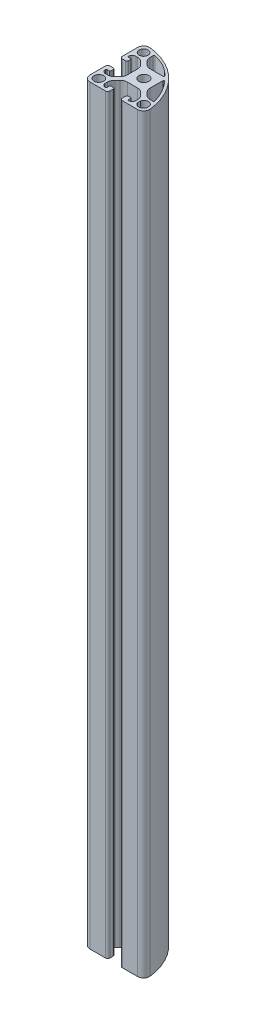
SolidWorks part; units mm, degrees
ref_plane "Alzado" through (0, 0, 0) normal (0, 0, 1) x (1, 0, 0)
ref_plane "Planta" through (0, 0, 0) normal (0, 1, 0) x (1, 0, 0)
ref_plane "Vista lateral" through (0, 0, 0) normal (1, 0, 0) x (0, 0, -1)
sketch "Croquis1" plane through (0, 0, 0) normal (0, 1, 0) x (1, 0, 0)
  line L0 (-18.2, 12.3) -> (-18.2, 15.7771)
  line L1 (-12.3, 11.8) -> (-17.7, 11.8)
  line L2 (-11.8, 16.9053) -> (-11.8, 12.3)
  line L3 (11.8, -17.7) -> (11.8, -12.3)
  line L4 (15.7771, -18.2) -> (12.3, -18.2)
  line L5 (12.3, -11.8) -> (16.9053, -11.8)
  line L6 (-18.2, -16) -> (-18.2, -12.3)
  line L7 (-12.3, -18.2) -> (-16, -18.2)
  line L8 (-11.8, -12.3) -> (-11.8, -17.7)
  line L9 (-17.7, -11.8) -> (-12.3, -11.8)
  line L10 (-10.1, 14.2924) -> (-10.1, 16.2371)
  line L11 (-6.9431, 9.0645) -> (-8.6355, 10.7569)
  line L12 (5.1332, 7.6) -> (-3.4076, 7.6)
  line L13 (4.1, -16.35) -> (4.1, -18.5)
  line L14 (5.6, -20) -> (15.7771, -20)
  line L15 (-20, 15.7771) -> (-20, 5.6)
  line L16 (-18.5, 4.1) -> (-16.35, 4.1)
  line L17 (-15.35, 5.1) -> (-15.35, 6.6)
  line L18 (-15.85, 7.1) -> (-17.5, 7.1)
  line L19 (-15.5, 10.1) -> (-14.2924, 10.1)
  line L20 (-10.7569, 8.6355) -> (-9.0645, 6.9431)
  line L21 (-7.6, 3.4076) -> (-7.6, -3.4076)
  line L22 (-9.0645, -6.9431) -> (-10.7569, -8.6355)
  line L23 (-14.2924, -10.1) -> (-15.5, -10.1)
  line L24 (-17.5, -7.1) -> (-15.85, -7.1)
  line L25 (-15.35, -6.6) -> (-15.35, -5.1)
  line L26 (-16.35, -4.1) -> (-18.5, -4.1)
  line L27 (-20, -5.6) -> (-20, -16)
  line L28 (-16, -20) -> (-5.6, -20)
  line L29 (-4.1, -18.5) -> (-4.1, -16.35)
  line L30 (-5.1, -15.35) -> (-6.6, -15.35)
  line L31 (-7.1, -15.85) -> (-7.1, -17.5)
  line L32 (-10.1, -15.5) -> (-10.1, -14.2924)
  line L33 (-8.6355, -10.7569) -> (-6.9431, -9.0645)
  line L34 (-3.4076, -7.6) -> (3.4076, -7.6)
  line L35 (6.9431, -9.0645) -> (8.6355, -10.7569)
  line L36 (10.1, -14.2924) -> (10.1, -15.5)
  line L37 (7.1, -17.5) -> (7.1, -15.85)
  line L38 (6.6, -15.35) -> (5.1, -15.35)
  line L39 (16.2371, -10.1) -> (14.2924, -10.1)
  line L40 (10.7569, -8.6355) -> (9.0645, -6.9431)
  line L41 (7.6, -3.4076) -> (7.6, 5.1332)
  circle A0 centre (0, 0) radius 3.35
  arc A1 (-15.7556, 17.9635) -> (-18.2, 15.7771) centre (-16, 15.7771) ccw
  arc A2 (-18.2, 12.3) -> (-17.7, 11.8) centre (-17.7, 12.3) ccw
  arc A3 (-12.3, 11.8) -> (-11.8, 12.3) centre (-12.3, 12.3) ccw
  arc A4 (-11.8, 16.9053) -> (-12.1979, 17.3947) centre (-12.3, 16.9053) ccw
  arc A5 (-12.1979, 17.3947) -> (-15.7556, 17.9635) centre (-20, -20) ccw
  arc A6 (12.3, -11.8) -> (11.8, -12.3) centre (12.3, -12.3) ccw
  arc A7 (11.8, -17.7) -> (12.3, -18.2) centre (12.3, -17.7) ccw
  arc A8 (15.7771, -18.2) -> (17.9635, -15.7556) centre (15.7771, -16) ccw
  arc A9 (17.9635, -15.7556) -> (17.3947, -12.1979) centre (-20, -20) ccw
  arc A10 (17.3947, -12.1979) -> (16.9053, -11.8) centre (16.9053, -12.3) ccw
  arc A11 (-17.7, -11.8) -> (-18.2, -12.3) centre (-17.7, -12.3) ccw
  arc A12 (-18.2, -16) -> (-16, -18.2) centre (-16, -16) ccw
  arc A13 (-12.3, -18.2) -> (-11.8, -17.7) centre (-12.3, -17.7) ccw
  arc A14 (-11.8, -12.3) -> (-12.3, -11.8) centre (-12.3, -12.3) ccw
  arc A15 (4.1, -18.5) -> (5.6, -20) centre (5.6, -18.5) ccw
  arc A16 (15.7771, -20) -> (19.7523, -15.5556) centre (15.7771, -16) ccw
  arc A17 (19.7523, -15.5556) -> (-15.5556, 19.7523) centre (-20, -20) ccw
  arc A18 (-15.5556, 19.7523) -> (-20, 15.7771) centre (-16, 15.7771) ccw
  arc A19 (-20, 5.6) -> (-18.5, 4.1) centre (-18.5, 5.6) ccw
  arc A20 (-16.35, 4.1) -> (-15.35, 5.1) centre (-16.35, 5.1) ccw
  arc A21 (-15.35, 6.6) -> (-15.85, 7.1) centre (-15.85, 6.6) ccw
  arc A22 (-18, 7.6) -> (-17.5, 7.1) centre (-17.5, 7.6) ccw
  arc A23 (-15.5, 10.1) -> (-18, 7.6) centre (-15.5, 7.6) ccw
  arc A24 (-10.7569, 8.6355) -> (-14.2924, 10.1) centre (-14.2924, 5.1) ccw
  arc A25 (-7.6, 3.4076) -> (-9.0645, 6.9431) centre (-12.6, 3.4076) ccw
  arc A26 (-9.0645, -6.9431) -> (-7.6, -3.4076) centre (-12.6, -3.4076) ccw
  arc A27 (-14.2924, -10.1) -> (-10.7569, -8.6355) centre (-14.2924, -5.1) ccw
  arc A28 (-18, -7.6) -> (-15.5, -10.1) centre (-15.5, -7.6) ccw
  arc A29 (-17.5, -7.1) -> (-18, -7.6) centre (-17.5, -7.6) ccw
  arc A30 (-15.85, -7.1) -> (-15.35, -6.6) centre (-15.85, -6.6) ccw
  arc A31 (-15.35, -5.1) -> (-16.35, -4.1) centre (-16.35, -5.1) ccw
  arc A32 (-18.5, -4.1) -> (-20, -5.6) centre (-18.5, -5.6) ccw
  arc A33 (-20, -16) -> (-16, -20) centre (-16, -16) ccw
  arc A34 (-5.6, -20) -> (-4.1, -18.5) centre (-5.6, -18.5) ccw
  arc A35 (-4.1, -16.35) -> (-5.1, -15.35) centre (-5.1, -16.35) ccw
  arc A36 (-6.6, -15.35) -> (-7.1, -15.85) centre (-6.6, -15.85) ccw
  arc A37 (-7.6, -18) -> (-7.1, -17.5) centre (-7.6, -17.5) ccw
  arc A38 (-10.1, -15.5) -> (-7.6, -18) centre (-7.6, -15.5) ccw
  arc A39 (-8.6355, -10.7569) -> (-10.1, -14.2924) centre (-5.1, -14.2924) ccw
  arc A40 (-3.4076, -7.6) -> (-6.9431, -9.0645) centre (-3.4076, -12.6) ccw
  arc A41 (6.9431, -9.0645) -> (3.4076, -7.6) centre (3.4076, -12.6) ccw
  arc A42 (10.1, -14.2924) -> (8.6355, -10.7569) centre (5.1, -14.2924) ccw
  arc A43 (7.6, -18) -> (10.1, -15.5) centre (7.6, -15.5) ccw
  arc A44 (7.1, -17.5) -> (7.6, -18) centre (7.6, -17.5) ccw
  arc A45 (7.1, -15.85) -> (6.6, -15.35) centre (6.6, -15.85) ccw
  arc A46 (5.1, -15.35) -> (4.1, -16.35) centre (5.1, -16.35) ccw
  arc A47 (-9.4621, 16.7177) -> (-10.1, 16.2371) centre (-9.6, 16.2371) ccw
  arc A48 (-10.1, 14.2924) -> (-8.6355, 10.7569) centre (-5.1, 14.2924) ccw
  arc A49 (-6.9431, 9.0645) -> (-3.4076, 7.6) centre (-3.4076, 12.6) ccw
  arc A50 (5.1332, 7.6) -> (5.4666, 8.4727) centre (5.1332, 8.1) ccw
  arc A51 (16.7177, -9.4621) -> (8.4727, 5.4666) centre (-20, -20) ccw
  arc A52 (16.2371, -10.1) -> (16.7177, -9.4621) centre (16.2371, -9.6) ccw
  arc A53 (10.7569, -8.6355) -> (14.2924, -10.1) centre (14.2924, -5.1) ccw
  arc A54 (7.6, -3.4076) -> (9.0645, -6.9431) centre (12.6, -3.4076) ccw
  arc A55 (8.4727, 5.4666) -> (7.6, 5.1332) centre (8.1, 5.1332) ccw
  arc A56 (-9.4621, 16.7177) -> (5.4666, 8.4727) centre (-14.5044, -10.0495) cw
extrude "Saliente-Extruir1" add sketch "Croquis1" along normal blind 500
sketch "Croquis2" plane through (0, 500, 0) normal (0, 1, 0) x (1, 0, 0)
  line L0 (-18.2, 15.7771) -> (-18.2, 12.3) construction
  line L1 (-17.7, 11.8) -> (-12.3, 11.8) construction
  line L2 (-11.8, 12.3) -> (-11.8, 16.9053) construction
  line L3 (-18.2, 15.7771) -> (-18.2, 12.3)
  line L4 (-17.7, 11.8) -> (-12.3, 11.8)
  line L5 (-11.8, 12.3) -> (-11.8, 16.9053)
  line L6 (-16, -18.2) -> (-12.3, -18.2) construction
  line L7 (-18.2, -12.3) -> (-18.2, -16) construction
  line L8 (-12.3, -11.8) -> (-17.7, -11.8) construction
  line L9 (-11.8, -17.7) -> (-11.8, -12.3) construction
  line L10 (-16, -18.2) -> (-12.3, -18.2)
  line L11 (-18.2, -12.3) -> (-18.2, -16)
  line L12 (-12.3, -11.8) -> (-17.7, -11.8)
  line L13 (-11.8, -17.7) -> (-11.8, -12.3)
  line L14 (12.3, -18.2) -> (15.7771, -18.2) construction
  line L15 (11.8, -12.3) -> (11.8, -17.7) construction
  line L16 (16.9053, -11.8) -> (12.3, -11.8) construction
  line L17 (12.3, -18.2) -> (15.7771, -18.2)
  line L18 (11.8, -12.3) -> (11.8, -13.9666)
  line L19 (16.9053, -11.8) -> (12.3, -11.8)
  line L20 (11.8, -16.0334) -> (11.8, -17.7)
  arc A0 (-11.8, 16.9053) -> (-12.1979, 17.3947) centre (-12.3, 16.9053) ccw construction
  arc A1 (-12.1979, 17.3947) -> (-15.7556, 17.9635) centre (-20, -20) ccw construction
  arc A2 (-15.7556, 17.9635) -> (-18.2, 15.7771) centre (-16, 15.7771) ccw construction
  arc A3 (-18.2, 12.3) -> (-17.7, 11.8) centre (-17.7, 12.3) ccw construction
  arc A4 (-12.3, 11.8) -> (-11.8, 12.3) centre (-12.3, 12.3) ccw construction
  arc A5 (-11.8, 16.9053) -> (-12.1979, 17.3947) centre (-12.3, 16.9053) ccw
  arc A6 (-12.1979, 17.3947) -> (-15.7556, 17.9635) centre (-20, -20) ccw
  arc A7 (-15.7556, 17.9635) -> (-18.2, 15.7771) centre (-16, 15.7771) ccw
  arc A8 (-18.2, 12.3) -> (-17.7, 11.8) centre (-17.7, 12.3) ccw
  arc A9 (-12.3, 11.8) -> (-11.8, 12.3) centre (-12.3, 12.3) ccw
  arc A10 (-12.3, -18.2) -> (-11.8, -17.7) centre (-12.3, -17.7) ccw construction
  arc A11 (-18.2, -16) -> (-16, -18.2) centre (-16, -16) ccw construction
  arc A12 (-17.7, -11.8) -> (-18.2, -12.3) centre (-17.7, -12.3) ccw construction
  arc A13 (-11.8, -12.3) -> (-12.3, -11.8) centre (-12.3, -12.3) ccw construction
  arc A14 (-12.3, -18.2) -> (-11.8, -17.7) centre (-12.3, -17.7) ccw
  arc A15 (-18.2, -16) -> (-16, -18.2) centre (-16, -16) ccw
  arc A16 (-17.7, -11.8) -> (-18.2, -12.3) centre (-17.7, -12.3) ccw
  arc A17 (-11.8, -12.3) -> (-12.3, -11.8) centre (-12.3, -12.3) ccw
  arc A18 (17.3947, -12.1979) -> (16.9053, -11.8) centre (16.9053, -12.3) ccw construction
  arc A19 (17.9635, -15.7556) -> (17.3947, -12.1979) centre (-20, -20) ccw construction
  arc A20 (15.7771, -18.2) -> (17.9635, -15.7556) centre (15.7771, -16) ccw construction
  arc A21 (11.8, -17.7) -> (12.3, -18.2) centre (12.3, -17.7) ccw construction
  arc A22 (12.3, -11.8) -> (11.8, -12.3) centre (12.3, -12.3) ccw construction
  arc A23 (17.3947, -12.1979) -> (16.9053, -11.8) centre (16.9053, -12.3) ccw
  arc A24 (17.9635, -15.7556) -> (17.9551, -15.6816) centre (-20, -20) ccw
  arc A25 (15.7771, -18.2) -> (17.9635, -15.7556) centre (15.7771, -16) ccw
  arc A26 (11.8, -17.7) -> (12.3, -18.2) centre (12.3, -17.7) ccw
  arc A27 (12.3, -11.8) -> (11.8, -12.3) centre (12.3, -12.3) ccw
  circle A28 centre (-14.9928, 14.8209) radius 3.0209
  circle A29 centre (-15, -15) radius 3.2
  circle A30 centre (14.8285, -15) radius 3.2
  arc A31 (17.6371, -13.4664) -> (17.3947, -12.1979) centre (-20, -20) ccw
extrude "Saliente-Extruir2" add sketch "Croquis2" against normal up to surface (500 mm away) contours A29 L13 A17 L12 | A29 L10 A14 L13 | A29 L11 A15 L10 | A29 L12 A16 L11 | A28 A6 A7 L3 A8 L4 | A28 L4 A9 L5 A5 A6 | A30 A31 A23 L19 | A30 L19 A27 L18 | A30 L20 A26 L17 | A30 L17 A25 A24 region at (-17.4189, 500, -17.3634) region at (-13.3889, 500, -17.5545) region at (-17.285, 500, 17.285) region at (-12.5299, 500, 17.4701) region at (-17.4701, 500, 12.5299) region at (-12.5299, 500, 12.5299) region at (12.5158, 500, 17.6045) region at (17.0357, 500, 17.362) region at (12.5158, 500, 12.3955) region at (16.8311, 500, 12.2576) up to face at (-4.7129, 0, -11.4358)
